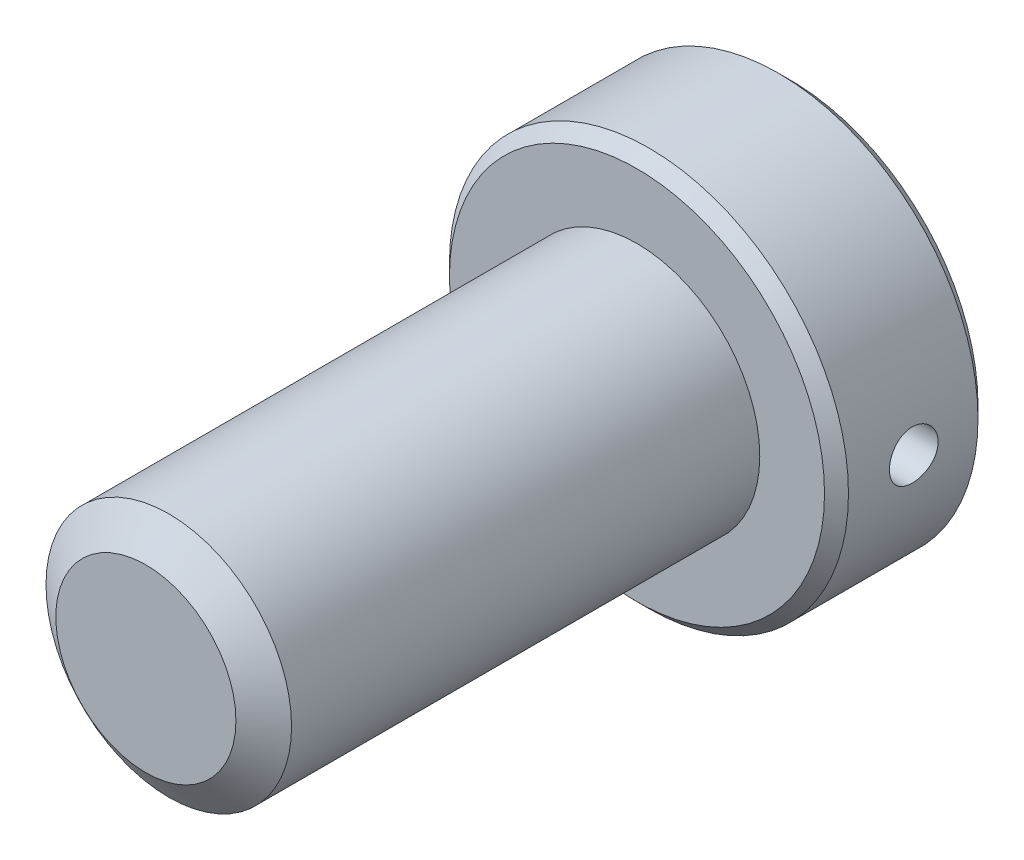
SolidWorks part; units mm, degrees
material "Alloy Steel"
ref_plane "Front Plane" through (0, 0, 0) normal (0, 0, 1) x (1, 0, 0)
ref_plane "Top Plane" through (0, 0, 0) normal (0, 1, 0) x (1, 0, 0)
ref_plane "Right Plane" through (0, 0, 0) normal (1, 0, 0) x (0, 0, -1)
sketch "Sketch1" plane through (0, 0, 0) normal (0, 0, 1) x (1, 0, 0)
  circle A0 centre (0, 0) radius 4
  dimension "OD" = 8
extrude "Extrude1" add sketch "Sketch1" against normal blind 16
sketch "Sketch2" plane through (0, 0, 0) normal (0, 0, 1) x (1, 0, 0)
  circle A0 centre (0, 0) radius 4 construction
  circle A1 centre (0, 0) radius 4
curve "Helix/Spiral1" pitch 1.25 height 17.25 turns 13.8 parameters "pitch"=1.25
sketch "Sketch3" plane through (0, 0, 0) normal (1, 0, 0) x (0, 0, -1)
  line L0 (-1.0938, 4) -> (-0.625, 3.1881)
  line L1 (-0.625, 3.1881) -> (-0.4688, 3.1881)
  line L2 (-0.4688, 3.1881) -> (0, 4)
  line L3 (-1.0938, 4) -> (0, 4)
  line L4 (-0.5469, 4) -> (-0.5469, 3.1881) construction
  line L5 (-0.8594, 3.5941) -> (-0.2344, 3.5941) construction
  line L6 (0, 4) -> (0, -4) construction
  line L7 (0, -4) -> (16, -4) construction
  point P11 (5.625, -4)
  dimension "D1" = 0.1562
  dimension "D2" = 0.625
  dimension "D3" = 60
  dimension "D4" = 5.625
sweep "Cut-Sweep1" [suppressed] cut profiles "Sketch3" path "Helix/Spiral1"
sketch "Sketch4" plane through (0, 0, 0) normal (1, 0, 0) x (0, 0, -1)
  line L0 (0.7464, 4) -> (0, 2.9341)
  line L1 (0, 2.9341) -> (0, 4)
  line L2 (0.7464, 4) -> (0, 4)
  line L3 (-1.0938, 4) -> (0, 4) construction
  line L4 (0, 0) -> (7.0209, 0) construction
  dimension "D1" = 55
  dimension "D2" = 0.254
revolve "Cut-Revolve1" cut sketch "Sketch4" angle 360 about L4
sketch "Sketch5" [suppressed] plane through (0, 0, 0) normal (1, 0, 0) x (0, 0, -1)
  line L0 (16, -3.6352) -> (16, -0.9564) construction
  line L1 (16, 4) -> (0.1203, 4)
  line L2 (16, 4) -> (16, 0)
  line L3 (16, 0) -> (0.0001, 0)
  line L4 (0.0001, 3.6698) -> (0.0001, 0)
  line L5 (0.1203, 4) -> (0.0001, 3.6698)
  line L6 (0, 0) -> (9.9695, 0) construction
  point P3 (0.0001, 4)
  point P10 (0.0001, 4)
  dimension "D1" = 0.3302
  dimension "Thread min" = 0.0001
  dimension "D3" = 20
revolve "partially thread" [suppressed] add sketch "Sketch5" angle 360 about L6
sketch "Sketch6" plane through (0, 0, -16) normal (0, 0, -1) x (-1, 0, 0)
  circle A0 centre (0, 0) radius 6.5
  dimension "head dia" = 13
extrude "Extrude2" add sketch "Sketch6" along normal blind 5
sketch "Sketch7" plane through (0, 0, -21) normal (0, 0, -1) x (-1, 0, 0)
  line L1 (0, 3.4641) -> (-3, 1.7321)
  line L2 (-3, 1.7321) -> (-3, -1.7321)
  line L3 (-3, -1.7321) -> (0, -3.4641)
  line L4 (0, -3.4641) -> (3, -1.7321)
  line L5 (3, -1.7321) -> (3, 1.7321)
  line L6 (3, 1.7321) -> (0, 3.4641)
  circle A0 centre (0, 0) radius 3 construction
  dimension "hex dia" = 6
extrude "Cut-Extrude1" cut sketch "Sketch7" against normal blind 4.5
sketch "Sketch8" plane through (0, 0, -21) normal (0, 0, -1) x (-1, 0, 0)
  circle A0 centre (0, 0) radius 3.4641
extrude "Cut-Extrude2" cut sketch "Sketch8" against normal through all draft 45
chamfer "Chamfer1" distance 0.39 angle 45 2 edges at (-6.5, 0, -21) (-6.5, 0, -16)
sketch "Sketch9" [suppressed] plane through (0, 0, 0) normal (1, 0, 0) x (0, 0, -1)
  line L0 (0, 4) -> (0, -4) construction
  line L1 (6.875, 4) -> (6.875, -4) construction
  dimension "D1" = 6.875
sketch "Sketch10" plane through (0, 0, 0) normal (1, 0, 0) x (0, 0, -1)
  line L0 (16, 4) -> (16, 0)
  line L1 (16, 4) -> (15.6875, 4)
  line L2 (15.6875, 4) -> (14.0306, 0)
  line L3 (16, 0) -> (14.0306, 0)
  line L4 (16, 6.11) -> (16, -6.11) construction
  dimension "D1" = 22.5
  dimension "D2" = 0.3125
revolve "Revolve1" [suppressed] add sketch "Sketch10" angle 360 about L3
sketch "Sketch11" plane through (0, 0, 0) normal (1, 0, 0) x (0, -1, 0)
  line L0 (0, 20.5359) -> (0, 16.5) construction
  line L4 (-1.7321, 16.5) -> (1.7321, 16.5) construction
  circle A0 centre (0, 18.5179) radius 0.7937
  spline S0 degree 3 poles (-1.7321, 21) (-1.5981, 20.933) (-1.4615, 20.8705) (-1.1813, 20.7576) (-1.0371, 20.7071) (-0.6018, 20.583) (-0.3052, 20.5359) (0.3048, 20.5359) (0.6022, 20.5831) (1.1811, 20.7481) (1.4637, 20.8658) (1.7321, 21) knots 0 0 0 0 0.125 0.125 0.25 0.25 0.5 0.5 0.75 0.75 1 1 1 1 construction
  point P15 (0, 18.5179)
  point P24 (0, 16.5)
  dimension "D1" = 1.5875
extrude "Cut-Extrude3" cut sketch "Sketch11" against normal through all both and the other way through all
equation "\"D3@Helix/Spiral1\" = \"screw length@Extrude1\"+\"pitch@Helix/Spiral1\""
equation "\"D1@Sketch3\" = \"pitch@Helix/Spiral1\"*.125"
equation "\"D2@Sketch3\" = \"pitch@Helix/Spiral1\"*.5"
equation "\"D1@Cut-Extrude1\" = \"hex dia@Sketch7\"*.75"
equation "\"D1@Chamfer1\" = \"head dia@Sketch6\"*.03"
equation "\"D1@Sketch9\" = \"pitch@Helix/Spiral1\"*5.5"
equation "\"D2@Sketch10\" = \"pitch@Helix/Spiral1\"*.25"
equation "\"D4@Sketch3\" = \"pitch@Helix/Spiral1\"*4.50"
